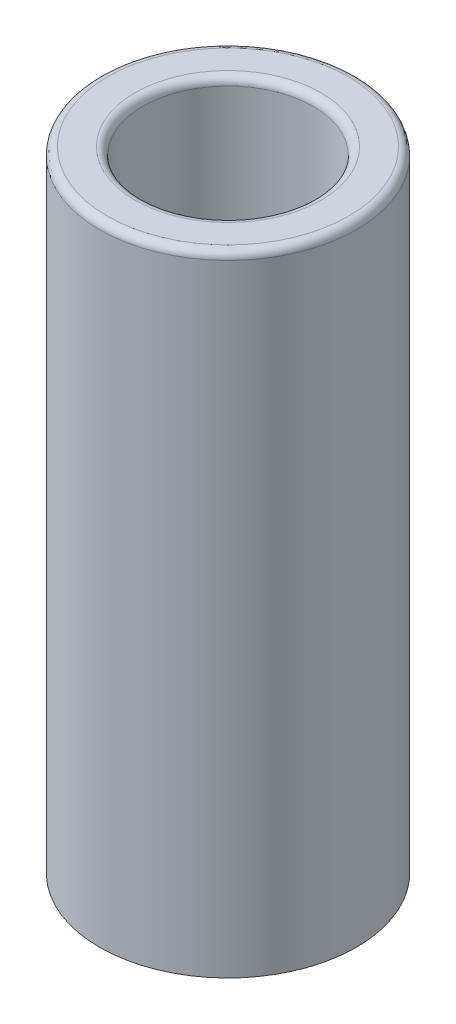
SolidWorks part; units mm, degrees
ref_plane "Front Plane" through (0, 0, 0) normal (0, 0, 1) x (1, 0, 0)
ref_plane "Top Plane" through (0, 0, 0) normal (0, 1, 0) x (1, 0, 0)
ref_plane "Right Plane" through (0, 0, 0) normal (1, 0, 0) x (0, 0, -1)
sketch "Sketch1" plane through (0, 0, 0) normal (0, 1, 0) x (1, 0, 0)
  circle A0 centre (0, 0) radius 2.45
  circle A1 centre (0, 0) radius 1.625
  dimension "D1" = 4.9
  dimension "D2" = 3.25
extrude "Boss-Extrude1" add sketch "Sketch1" along normal blind 12
extrude "Boss-Extrude2" add sketch "Sketch1<4>" along normal offset from surface (3 mm away) 9 contours A1 region at (0, 0, 0) up to face at (0, 12, 2.45)
sketch "Sketch1<4>" plane through (0, 0, 0) normal (0, 1, 0) x (1, 0, 0) same geometry as "Sketch1"
fillet "Fillet1" radius 0.15 2 edges at (0, 12, 1.625) (0, 12, 2.45)
